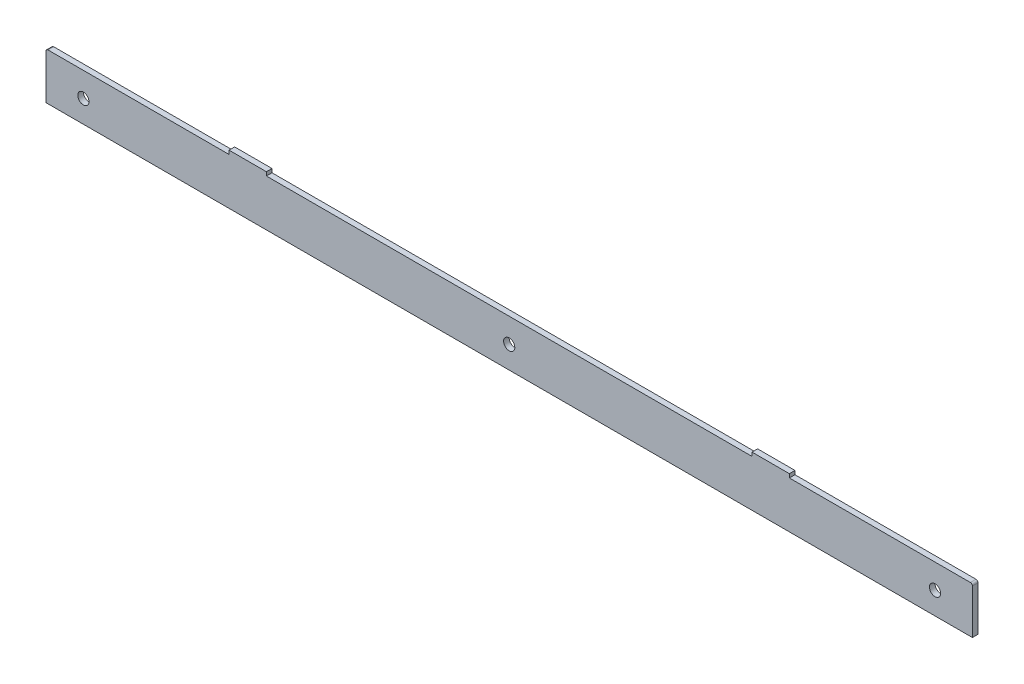
SolidWorks part; units mm, degrees
ref_plane "Спереди" through (0, 0, 0) normal (0, 0, 1) x (1, 0, 0)
ref_plane "Сверху" through (0, 0, 0) normal (0, 1, 0) x (1, 0, 0)
ref_plane "Справа" through (0, 0, 0) normal (1, 0, 0) x (0, 0, -1)
sketch "Эскиз1" plane through (0, 0, 0) normal (0, 0, 1) x (1, 0, 0)
  line L1 (-52.7153, 26.1806) -> (441.0847, 26.1806)
  line L2 (-53.8153, 25.0806) -> (-53.8153, 1.1806)
  line L3 (-53.8153, 1.1806) -> (442.1847, 1.1806)
  line L4 (442.1847, 25.0806) -> (442.1847, 1.1806)
  arc A0 (442.1847, 25.0806) -> (441.0847, 26.1806) centre (441.0847, 25.0806) ccw
  arc A1 (-53.8153, 25.0806) -> (-52.7153, 26.1806) centre (-52.7153, 25.0806) cw
  point P6 (442.1847, 26.1806)
  point P9 (-53.8153, 26.1806)
  dimension "D3" = 1.1
  dimension "D1" = 496
  dimension "D2" = 25
sheet metal parameters "Листовой металл1" thickness 3 parameters "D1"=1.1, "Толщина"=3
base flange "Базовая кромка1" sketch "Эскиз1" thickness 3 reverse thickness direction no parameters "D1"=1.1
sketch "Эскиз4" plane through (0, 26.1806, 0) normal (0, 1, 0) x (1, 0, 0)
  line L0 (194.1847, 3) -> (194.1847, 0) construction
  line L1 (441.0847, 3) -> (-52.7153, 3) construction
  line L2 (441.0847, 0) -> (-52.7153, 0) construction
  line L4 (44.1847, 3) -> (64.1847, 3)
  line L5 (44.1847, 3) -> (44.1847, 0)
  line L6 (44.1847, 0) -> (64.1847, 0)
  line L7 (64.1847, 3) -> (64.1847, 0)
  line L8 (324.1847, 3) -> (344.1847, 3)
  line L9 (324.1847, 3) -> (324.1847, 0)
  line L10 (324.1847, 0) -> (344.1847, 0)
  line L11 (344.1847, 3) -> (344.1847, 0)
  point P16 (204.3959, -2.571)
  dimension "D1" = 20
  dimension "D2" = 20
  dimension "D3" = 130
  dimension "D4" = 130
extrude "Бобышка-Вытянуть1" add sketch "Эскиз4" along normal blind 2
sketch "Эскиз5" plane through (0, 0, -3) normal (0, 0, -1) x (-1, 0, 0)
  line L0 (-442.1847, 13.1306) -> (53.8153, 13.1306) construction
  line L1 (-442.1847, 1.1806) -> (-442.1847, 25.0806) construction
  line L2 (53.8153, 25.0806) -> (53.8153, 1.1806) construction
  line L3 (-194.1847, 26.1806) -> (-194.1847, 1.1806) construction
  line L4 (-324.1847, 26.1806) -> (-64.1847, 26.1806) construction
  line L5 (53.8153, 1.1806) -> (-442.1847, 1.1806) construction
  circle A0 centre (-422.1847, 13.1306) radius 3
  circle A1 centre (-194.1847, 13.1306) radius 3
  circle A2 centre (33.8153, 13.1306) radius 3
  dimension "D1" = 6
  dimension "D2" = 6
  dimension "D3" = 6
  dimension "D4" = 20
  dimension "D5" = 20
extrude "Вырез-Вытянуть1" cut sketch "Эскиз5" against normal blind 10 normal cut yes
flat pattern "Развертка1" [suppressed]
sketch "Сгиб-Линии1" plane through (0, 0, 0) normal (0, 1, 0) x (1, 0, 0)
sketch3d "Граничная рамка1" [suppressed]
  line L0 (1.1, 1.1, 0) -> (-494.9, 1.0995, 0) construction
  line L1 (1.1, -24.8995, 0) -> (-494.9, -24.9, 0) construction
  line L2 (1.1, 1.1, 0) -> (1.1, -24.8995, 0) construction
  line L3 (-494.9, 1.0995, 0) -> (-494.9, -24.9, 0) construction
